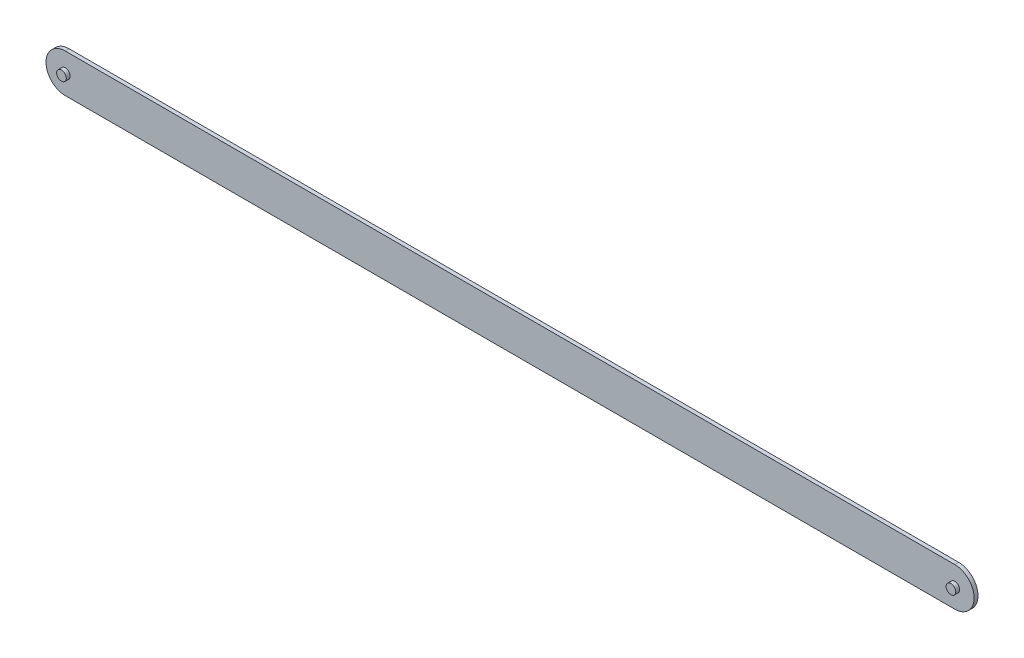
SolidWorks part; units mm, degrees
ref_plane "Front" through (0, 0, 0) normal (0, 0, 1) x (1, 0, 0)
ref_plane "Top" through (0, 0, 0) normal (0, 1, 0) x (1, 0, 0)
ref_plane "Right" through (0, 0, 0) normal (1, 0, 0) x (0, 0, -1)
sketch "Sketch2" plane through (0, 0, 0) normal (0, 0, 1) x (1, 0, 0)
  line L1 (0, 0) -> (584.2, 0)
  line L2 (0, 0) -> (0, 25.4)
  line L3 (0, 25.4) -> (584.2, 25.4)
  line L4 (584.2, 0) -> (584.2, 25.4)
  circle A0 centre (0, 12.7) radius 12.7
  circle A1 centre (584.2, 12.7) radius 12.7
  circle A2 centre (0, 12.7) radius 3.175
  circle A3 centre (584.2, 12.7) radius 3.175
  dimension "D2" = 6.35
  dimension "D1" = 25.4
  dimension "D3" = 584.2
extrude "Boss-Extrude1" add sketch "Sketch2" along normal blind 2.54 contours A1 L3 A0 L1 | A3 L4 A1 | A3 L4 A1 | A2 L2 A0 | A2 L2 A0 region at (292.1, 12.7, 0) region at (-5.6595, 12.7, 0) region at (5.6595, 12.7, 0) region at (578.5405, 12.7, 0) region at (589.8595, 12.7, 0)
extrude "Boss-Extrude2" add sketch "Sketch2<3>" along normal blind 5.08 contours L2 A2 | L2 A2 | L4 A3 | L4 A3 region at (-1.3475, 12.7, 0) region at (1.3475, 12.7, 0) region at (582.8525, 12.7, 0) region at (585.5475, 12.7, 0)
sketch "Sketch2<3>" plane through (0, 0, 0) normal (0, 0, 1) x (1, 0, 0) same geometry as "Sketch2"
